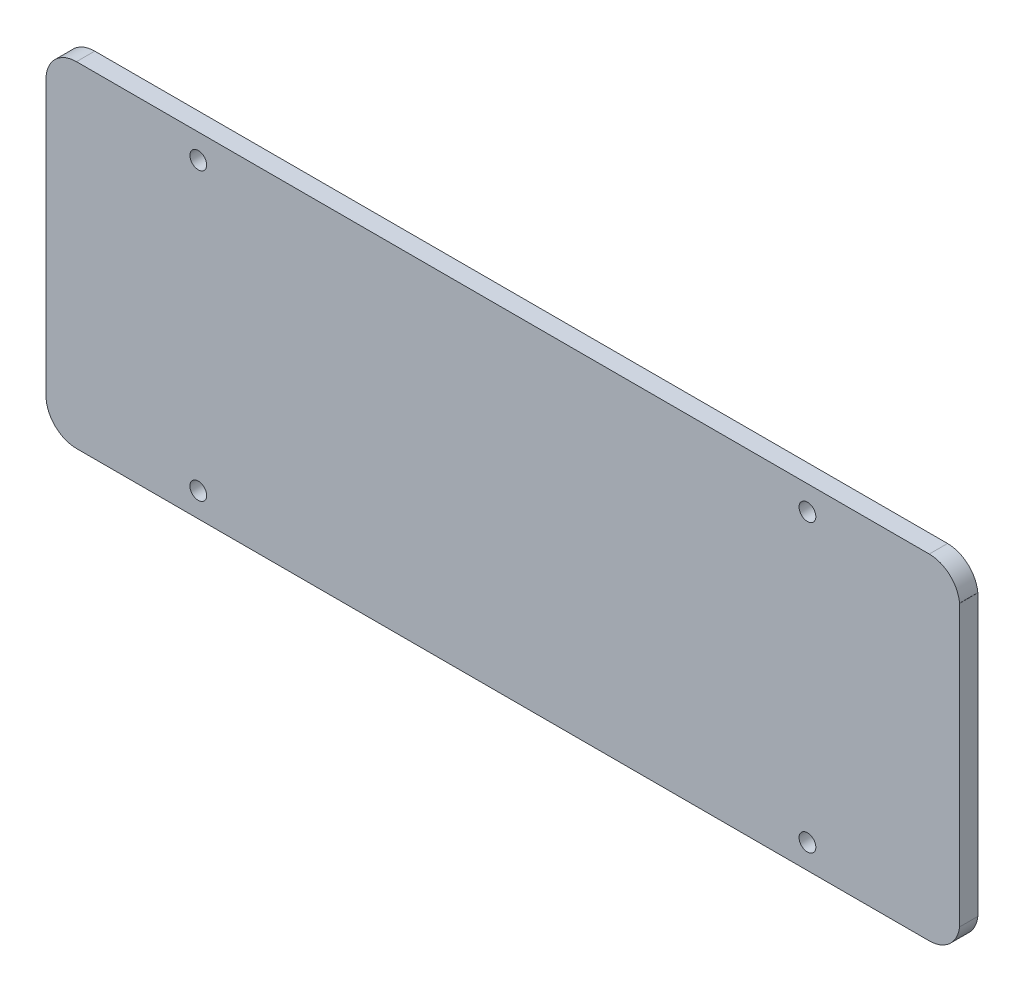
SolidWorks part; units mm, degrees
material "Aircraft Ply"
ref_plane "Front Plane" through (0, 0, 0) normal (0, 0, 1) x (1, 0, 0)
ref_plane "Top Plane" through (0, 0, 0) normal (0, 1, 0) x (1, 0, 0)
ref_plane "Right Plane" through (0, 0, 0) normal (1, 0, 0) x (0, 0, -1)
sketch "Sketch1" plane through (0, 0, 0) normal (0, 0, 1) x (1, 0, 0)
  line L0 (-75, 8) -> (75, 8) construction
  line L1 (-75, 0) -> (75, 0) construction
  line L8 (-75, 23) -> (-75, -23)
  line L9 (-44.3417, -23) -> (-25.6583, -23)
  line L10 (-14.3417, -23) -> (14.3417, -23)
  line L11 (25.6583, -23) -> (44.3417, -23)
  line L12 (75, -23) -> (75, 23)
  line L13 (44.3417, 23) -> (25.6583, 23)
  line L14 (14.3417, 23) -> (-14.3417, 23)
  line L15 (-25.6583, 23) -> (-44.3417, 23)
  line L16 (-75, 23) -> (-75, -23)
  line L17 (-44.3417, -23) -> (-25.6583, -23)
  line L18 (-14.3417, -23) -> (14.3417, -23)
  line L19 (25.6583, -23) -> (44.3417, -23)
  line L20 (75, -23) -> (75, 23)
  line L21 (44.3417, 23) -> (25.6583, 23)
  line L22 (14.3417, 23) -> (-14.3417, 23)
  line L23 (-25.6583, 23) -> (-44.3417, 23)
  line L30 (-75, -23) -> (-55.6583, -23)
  line L31 (-75, -23) -> (-55.6583, -23)
  line L32 (55.6583, -23) -> (75, -23)
  line L33 (55.6583, -23) -> (75, -23)
  line L34 (75, 23) -> (55.6583, 23)
  line L35 (75, 23) -> (55.6583, 23)
  line L36 (-55.6583, 23) -> (-75, 23)
  line L37 (-55.6583, 23) -> (-75, 23)
  line L38 (-54.25, 10.2535) -> (-54.25, 5.7465)
  line L39 (-61.75, 10.2535) -> (-61.75, 5.7465)
  line L40 (-29.75, 10.2535) -> (-29.75, 5.7465)
  line L41 (-22.25, 10.2535) -> (-22.25, 5.7465)
  line L42 (2.25, 10.2535) -> (2.25, 5.7465)
  line L43 (9.75, 10.2535) -> (9.75, 5.7465)
  line L44 (34.25, 10.2535) -> (34.25, 5.7465)
  line L45 (41.75, 10.2535) -> (41.75, 5.7465)
  line L46 (-13.75, -5.7465) -> (-13.75, -10.2535)
  line L47 (-6.25, -5.7465) -> (-6.25, -10.2535)
  line L48 (18.25, -5.7465) -> (18.25, -10.2535)
  line L49 (25.75, -5.7465) -> (25.75, -10.2535)
  line L50 (50.25, -5.7465) -> (50.25, -10.2535)
  line L51 (57.75, -5.7465) -> (57.75, -10.2535)
  line L52 (-45.75, -5.7465) -> (-45.75, -10.2535)
  line L53 (-38.25, -5.7465) -> (-38.25, -10.2535)
  circle A0 centre (-50, 23.5) radius 1.375 construction
  circle A1 centre (-20, 23.5) radius 1.375 construction
  circle A2 centre (20, 23.5) radius 1.375 construction
  circle A3 centre (50, 23.5) radius 1.375 construction
  circle A4 centre (50, -23.5) radius 1.375 construction
  circle A5 centre (20, -23.5) radius 1.375 construction
  circle A6 centre (-20, -23.5) radius 1.375 construction
  circle A7 centre (-50, -23.5) radius 1.375 construction
  circle A8 centre (-50, -23.5) radius 1.375
  circle A9 centre (-20, -23.5) radius 1.375
  circle A10 centre (20, -23.5) radius 1.375
  circle A11 centre (50, -23.5) radius 1.375
  circle A12 centre (50, 23.5) radius 1.375
  circle A13 centre (20, 23.5) radius 1.375
  circle A14 centre (-20, 23.5) radius 1.375
  circle A15 centre (-50, 23.5) radius 1.375
  circle A16 centre (-58, 8) radius 4.375
  circle A17 centre (-26, 8) radius 4.375
  circle A18 centre (6, 8) radius 4.375
  circle A19 centre (38, 8) radius 4.375
  circle A20 centre (-42, -8) radius 4.375
  circle A21 centre (-10, -8) radius 4.375
  circle A22 centre (22, -8) radius 4.375
  circle A23 centre (54, -8) radius 4.375
  arc A29 (-54, -23.5) -> (-55.6583, -23) centre (-55.6583, -26) ccw
  arc A30 (-54, -23.5) -> (-46, -23.5) centre (-50, -23.5) ccw
  arc A31 (-44.3417, -23) -> (-46, -23.5) centre (-44.3417, -26) ccw
  arc A32 (-24, -23.5) -> (-25.6583, -23) centre (-25.6583, -26) ccw
  arc A33 (-24, -23.5) -> (-16, -23.5) centre (-20, -23.5) ccw
  arc A34 (-14.3417, -23) -> (-16, -23.5) centre (-14.3417, -26) ccw
  arc A35 (16, -23.5) -> (14.3417, -23) centre (14.3417, -26) ccw
  arc A36 (16, -23.5) -> (24, -23.5) centre (20, -23.5) ccw
  arc A37 (25.6583, -23) -> (24, -23.5) centre (25.6583, -26) ccw
  arc A38 (46, -23.5) -> (44.3417, -23) centre (44.3417, -26) ccw
  arc A39 (46, -23.5) -> (54, -23.5) centre (50, -23.5) ccw
  arc A40 (55.6583, -23) -> (54, -23.5) centre (55.6583, -26) ccw
  arc A43 (54, 23.5) -> (55.6583, 23) centre (55.6583, 26) ccw
  arc A44 (54, 23.5) -> (46, 23.5) centre (50, 23.5) ccw
  arc A45 (44.3417, 23) -> (46, 23.5) centre (44.3417, 26) ccw
  arc A46 (24, 23.5) -> (25.6583, 23) centre (25.6583, 26) ccw
  arc A47 (24, 23.5) -> (16, 23.5) centre (20, 23.5) ccw
  arc A48 (14.3417, 23) -> (16, 23.5) centre (14.3417, 26) ccw
  arc A49 (-16, 23.5) -> (-14.3417, 23) centre (-14.3417, 26) ccw
  arc A50 (-16, 23.5) -> (-24, 23.5) centre (-20, 23.5) ccw
  arc A51 (-25.6583, 23) -> (-24, 23.5) centre (-25.6583, 26) ccw
  arc A52 (-46, 23.5) -> (-44.3417, 23) centre (-44.3417, 26) ccw
  arc A53 (-46, 23.5) -> (-54, 23.5) centre (-50, 23.5) ccw
  arc A54 (-55.6583, 23) -> (-54, 23.5) centre (-55.6583, 26) ccw
  arc A57 (-54, -23.5) -> (-55.6583, -23) centre (-55.6583, -26) ccw
  arc A58 (-54, -23.5) -> (-46, -23.5) centre (-50, -23.5) ccw
  arc A59 (-44.3417, -23) -> (-46, -23.5) centre (-44.3417, -26) ccw
  arc A60 (-24, -23.5) -> (-25.6583, -23) centre (-25.6583, -26) ccw
  arc A61 (-24, -23.5) -> (-16, -23.5) centre (-20, -23.5) ccw
  arc A62 (-14.3417, -23) -> (-16, -23.5) centre (-14.3417, -26) ccw
  arc A63 (16, -23.5) -> (14.3417, -23) centre (14.3417, -26) ccw
  arc A64 (16, -23.5) -> (24, -23.5) centre (20, -23.5) ccw
  arc A65 (25.6583, -23) -> (24, -23.5) centre (25.6583, -26) ccw
  arc A66 (46, -23.5) -> (44.3417, -23) centre (44.3417, -26) ccw
  arc A67 (46, -23.5) -> (54, -23.5) centre (50, -23.5) ccw
  arc A68 (55.6583, -23) -> (54, -23.5) centre (55.6583, -26) ccw
  arc A71 (54, 23.5) -> (55.6583, 23) centre (55.6583, 26) ccw
  arc A72 (54, 23.5) -> (46, 23.5) centre (50, 23.5) ccw
  arc A73 (44.3417, 23) -> (46, 23.5) centre (44.3417, 26) ccw
  arc A74 (24, 23.5) -> (25.6583, 23) centre (25.6583, 26) ccw
  arc A75 (24, 23.5) -> (16, 23.5) centre (20, 23.5) ccw
  arc A76 (14.3417, 23) -> (16, 23.5) centre (14.3417, 26) ccw
  arc A77 (-16, 23.5) -> (-14.3417, 23) centre (-14.3417, 26) ccw
  arc A78 (-16, 23.5) -> (-24, 23.5) centre (-20, 23.5) ccw
  arc A79 (-25.6583, 23) -> (-24, 23.5) centre (-25.6583, 26) ccw
  arc A80 (-46, 23.5) -> (-44.3417, 23) centre (-44.3417, 26) ccw
  arc A81 (-46, 23.5) -> (-54, 23.5) centre (-50, 23.5) ccw
  arc A82 (-55.6583, 23) -> (-54, 23.5) centre (-55.6583, 26) ccw
  dimension "D2" = 8.75
  dimension "D3" = 8
  dimension "D6" = 17
  dimension "D7" = 7.5
  dimension "D1" = 0
  dimension "D4" = 4
  dimension "D5" = 2
extrude "Boss-Extrude1" add sketch "Sketch1" along normal blind 3 contours A82 L37 L16 L31 A57 A58 A59 L17 A60 A61 A62 L18 A63 A64 A65 L19 A66 A67 A68 L33 L20 L35 A71 A72 A73 L21 A74 A75 A76 L22 A77 A78 A79 L23 A80 A81 A23 A22 A21 | L39 A16 | L38 A16 | L40 A17 | L41 A17 | L42 A18 | L43 A18 | L44 A19 | L45 A19 | L50 A23 | L51 A23 | L48 A22 | L49 A22 | L46 A21 | L47 A21 | L52 A20 | L53 A20 region at (0.1456, 0, 0) region at (-53.9984, 8, 0) region at (-62.0016, 8, 0) region at (-30.0016, 8, 0) region at (-21.9984, 8, 0) region at (1.9984, 8, 0) region at (10.0016, 8, 0) region at (33.9984, 8, 0) region at (42.0016, 8, 0) region at (-14.0016, -8, 0) region at (-5.9984, -8, 0) region at (17.9984, -8, 0) region at (26.0016, -8, 0) region at (49.9984, -8, 0) region at (58.0016, -8, 0) region at (-46.0016, -8, 0) region at (-37.9984, -8, 0)
sketch "Sketch2" plane through (0, 0, 3) normal (0, 0, 1) x (1, 0, 0)
  line L0 (-58, 8) -> (-42, -8) construction
  line L1 (-49.8527, 16.1473) -> (-33.8527, 0.1473)
  line L2 (-66.1473, -0.1473) -> (-50.1473, -16.1473)
  line L3 (-26, 8) -> (-10, -8) construction
  line L4 (-17.8527, 16.1473) -> (-1.8527, 0.1473)
  line L5 (-34.1473, -0.1473) -> (-18.1473, -16.1473)
  line L6 (22, -8) -> (6, 8) construction
  line L7 (13.8527, -16.1473) -> (-2.1473, -0.1473)
  line L8 (30.1473, 0.1473) -> (14.1473, 16.1473)
  line L9 (38, 8) -> (54, -8) construction
  line L10 (46.1473, 16.1473) -> (62.1473, 0.1473)
  line L11 (29.8527, -0.1473) -> (45.8527, -16.1473)
  arc A10 (-49.8527, 16.1473) -> (-66.1473, -0.1473) centre (-58, 8) ccw
  arc A11 (-50.1473, -16.1473) -> (-33.8527, 0.1473) centre (-42, -8) ccw
  arc A12 (-17.8527, 16.1473) -> (-34.1473, -0.1473) centre (-26, 8) ccw
  arc A13 (-18.1473, -16.1473) -> (-1.8527, 0.1473) centre (-10, -8) ccw
  arc A14 (13.8527, -16.1473) -> (30.1473, 0.1473) centre (22, -8) ccw
  arc A15 (14.1473, 16.1473) -> (-2.1473, -0.1473) centre (6, 8) ccw
  arc A16 (46.1473, 16.1473) -> (29.8527, -0.1473) centre (38, 8) ccw
  arc A17 (45.8527, -16.1473) -> (62.1473, 0.1473) centre (54, -8) ccw
  text T0 "      1" font "Century Gothic" height in points 18
  point P2 (-50, 0)
  point P7 (-18, 0)
  point P14 (14, 0)
  point P21 (46, 0)
sketch "Sketch3" plane through (0, 0, 0) normal (0, 0, 1) x (1, 0, 0)
  line L0 (75, -23) -> (75, 23) construction
  line L1 (-70, 27.5) -> (70, 27.5)
  line L2 (-75, 22.5) -> (-75, -22.5)
  line L3 (-70, -27.5) -> (70, -27.5)
  line L4 (75, 22.5) -> (75, -22.5)
  line L5 (-75, 23) -> (-75, -23) construction
  arc A0 (-46, 23.5) -> (-54, 23.5) centre (-50, 23.5) ccw construction
  arc A1 (-54, -23.5) -> (-46, -23.5) centre (-50, -23.5) ccw construction
  arc A2 (-75, -22.5) -> (-70, -27.5) centre (-70, -22.5) ccw
  arc A3 (70, -27.5) -> (75, -22.5) centre (70, -22.5) ccw
  arc A4 (70, 27.5) -> (75, 22.5) centre (70, 22.5) cw
  arc A5 (-70, 27.5) -> (-75, 22.5) centre (-70, 22.5) ccw
  circle A6 centre (-50, 23.5) radius 1.375
  circle A7 centre (50, 23.5) radius 1.375
  circle A8 centre (50, -23.5) radius 1.375
  circle A9 centre (-50, -23.5) radius 1.375
  dimension "D1" = 5
extrude "Boss-Extrude2" add sketch "Sketch3" along normal through all
equation "\"D6@Sketch1\"=(20+14)/2"
